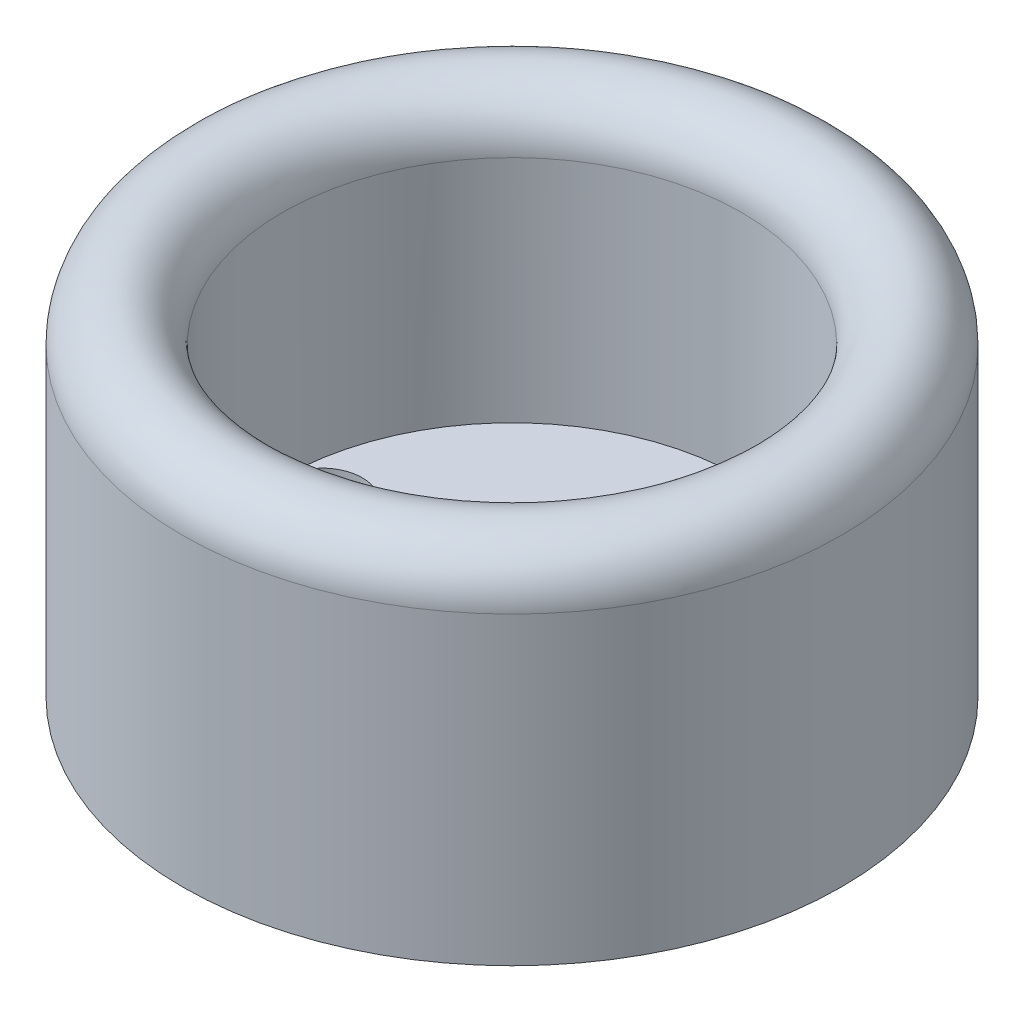
SolidWorks part; units mm, degrees
ref_plane "Front Plane" through (0, 0, 0) normal (0, 0, 1) x (1, 0, 0)
ref_plane "Top Plane" through (0, 0, 0) normal (0, 1, 0) x (1, 0, 0)
ref_plane "Right Plane" through (0, 0, 0) normal (1, 0, 0) x (0, 0, -1)
sketch "Sketch1" plane through (0, 0, 0) normal (0, 1, 0) x (1, 0, 0)
  line L1 (-29, -29) -> (29, -29) construction
  line L2 (-29, -29) -> (-29, 29) construction
  line L3 (-29, 29) -> (29, 29) construction
  line L4 (29, -29) -> (29, 29) construction
  line L5 (0, 29) -> (0, -29) construction
  line L6 (-29, 0) -> (29, 0) construction
  circle A0 centre (-19, 0) radius 1.8
  circle A1 centre (19, 0) radius 1.8
  circle A4 centre (0, 0) radius 5.5
  circle A5 centre (0, 0) radius 25
  point P0 (0, 0)
  dimension "D3" = 3.6
  dimension "D5" = 10
  dimension "D6" = 11
  dimension "D2" = 50
  dimension "D1" = 58
extrude "Boss-Extrude1" add sketch "Sketch1" along normal blind 7.5
sketch "Sketch2" plane through (0, 7.5, 0) normal (0, 1, 0) x (1, 0, 0)
  circle A4 centre (-19, 0) radius 4
  circle A5 centre (19, 0) radius 4
  dimension "D1" = 8
  dimension "D2" = 8
extrude "Cut-Extrude1" cut sketch "Sketch2" against normal blind 6
sketch "Sketch3" plane through (0, 0, 0) normal (0, -1, 0) x (1, 0, 0)
  circle A0 centre (0, 0) radius 33
  circle A1 centre (0, 0) radius 23
  circle A2 centre (-19, 0) radius 4 construction
  dimension "D1" = 10
extrude "Boss-Extrude2" add sketch "Sketch3" against normal blind 35.5
fillet "Fillet1" 2 edges at (0, 35.5, -33) (0, 35.5, -23) type full round first side face at (0, 35.5, -33) second side face at (0, 7.5, 0) middle face at (0, 35.5, -23)
